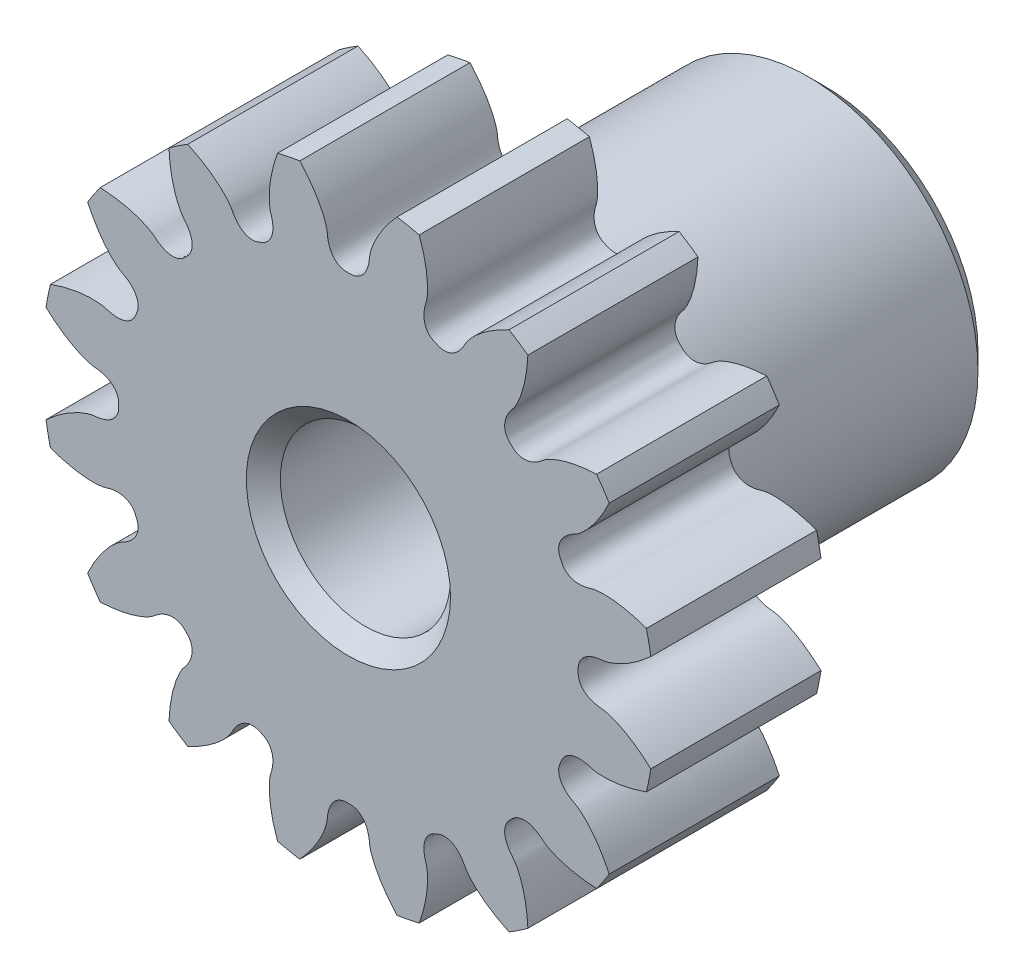
SolidWorks part; units mm, degrees
material "Plain Carbon Steel"
ref_plane "Front Plane" through (0, 0, 0) normal (0, 0, 1) x (1, 0, 0)
ref_plane "Top Plane" through (0, 0, 0) normal (0, 1, 0) x (1, 0, 0)
ref_plane "Right Plane" through (0, 0, 0) normal (1, 0, 0) x (0, 0, -1)
ref_axis "Axis1" through (0, 0, 55) along (0, 0, -1)
sketch "SketchRevolveSpur01" plane through (0, 0, 0) normal (1, 0, 0) x (0, 0, -1)
  line L0 (0, 0) -> (1, 0) construction
  line L1 (-2.5, 0) -> (-2.5, 9)
  line L2 (-2.5, 9) -> (2.5, 9)
  line L3 (2.5, 9) -> (2.5, 0)
  line L4 (2.5, 0) -> (-2.5, 0)
  dimension "Side1" = 2.5
  dimension "OutsideRadius" = 9
  dimension "Side2" = 2.5
revolve "Spur01" add sketch "SketchRevolveSpur01" angle 360 about L0
sketch "SketchToothSpur01" plane through (0, 0, 0) normal (0, 0, 1) x (1, 0, 0)
  arc A0 (8.93, 1.469) -> (8.93, -1.469) centre (0, 0) cw
  spline S0 degree 3 poles (8.93, -1.469) (8.852, -1.3959) (8.7347, -1.2926) (8.5758, -1.1667) (8.4638, -1.0839) (8.356, -1.0096) (8.2529, -0.9435) (8.1549, -0.8853) (8.0624, -0.8344) (7.9758, -0.7905) (7.8955, -0.7531) (7.8216, -0.7216) (7.7547, -0.6957) (7.6949, -0.6749) (7.6425, -0.6585) (7.5977, -0.6462) (7.5608, -0.6373) (7.5318, -0.6313) (7.4566, -0.6186) (7.3723, -0.6159) (7.2802, -0.5971) (7.2303, -0.5851) (7.1817, -0.5707) (7.1344, -0.554) (7.0881, -0.5345) (7.0427, -0.512) (6.998, -0.4858) (6.9542, -0.4551) (6.9112, -0.4189) (6.8697, -0.3762) (6.8308, -0.3256) (6.7965, -0.2661) (6.7692, -0.1978) (6.7539, -0.1268) (6.7487, -0.06) (6.7506, 0) (6.7487, 0.06) (6.7539, 0.1268) (6.7692, 0.1978) (6.7965, 0.2661) (6.8308, 0.3256) (6.8697, 0.3762) (6.9112, 0.4189) (6.9542, 0.4551) (6.998, 0.4858) (7.0427, 0.512) (7.0881, 0.5345) (7.1344, 0.554) (7.1817, 0.5707) (7.2303, 0.5851) (7.2802, 0.5971) (7.3723, 0.6159) (7.4566, 0.6186) (7.5318, 0.6313) (7.5608, 0.6373) (7.5977, 0.6462) (7.6425, 0.6585) (7.6949, 0.6749) (7.7547, 0.6957) (7.8216, 0.7216) (7.8955, 0.7531) (7.9758, 0.7905) (8.0624, 0.8344) (8.1549, 0.8853) (8.2529, 0.9435) (8.356, 1.0096) (8.4638, 1.0839) (8.5758, 1.1667) (8.7347, 1.2926) (8.852, 1.3959) (8.93, 1.469) knots 0 0 0 0 0.057702 0.084276 0.109331 0.132867 0.154885 0.175385 0.194366 0.211828 0.227772 0.242198 0.255105 0.266493 0.276364 0.284715 0.291548 0.296863 0.300659 0.332714 0.342111 0.351328 0.360412 0.369418 0.378417 0.387494 0.396754 0.406323 0.416348 0.426989 0.438404 0.450708 0.463926 0.47793 0.489703 0.5 0.510297 0.52207 0.536074 0.549292 0.561596 0.573011 0.583652 0.593677 0.603246 0.612506 0.621583 0.630582 0.639588 0.648672 0.657889 0.667286 0.699341 0.703137 0.708452 0.715285 0.723636 0.733507 0.744895 0.757802 0.772228 0.788172 0.805634 0.824615 0.845115 0.867133 0.890669 0.915724 0.942298 1 1 1 1
extrude "ToothExtrudeCutSpur01" cut sketch "SketchToothSpur01" against normal blind 2.5 and the other way blind 2.5
ref_axis "Axis2" through (9.9525, 0, 0) along (-1, 0, 0)
ref_plane "Plane1" through (0, 0, 0) normal (0, 0, -1) x (1, 0, 0)
pattern_circular "PatternSpur01" count 16 every 22.5 about axis through (0, 0, 55) along (0, 0, -1) of "ToothExtrudeCutSpur01"
sketch "HubSketchSide1" plane through (0, 0, 0) normal (1, 0, 0) x (0, 0, -1)
  line L0 (0, 0) -> (1, 0) construction
  line L1 (3, 5) -> (11, 5)
  line L2 (11, 5) -> (11.5, 4.5)
  line L3 (11.5, 4.5) -> (11.5, 0)
  line L4 (11.5, 0) -> (2.5, 0)
  line L5 (2.5, 0) -> (2.5, 5.5)
  arc A0 (2.5, 5.5) -> (3, 5) centre (3, 5.5) ccw
  dimension "HubFillet1" = 1
  dimension "HubRadius1" = 5
  dimension "HubChamferX1" = 0.5
  dimension "HubChamferY1" = 0.5
  dimension "HubFace1" = 11.5
  dimension "HubComponentFace1" = 2.5
revolve "HubRevolve1" add sketch "HubSketchSide1" angle 360 about L0
sketch "BoreRevolveSketch" plane through (0, 0, 0) normal (1, 0, 0) x (0, 0, -1)
  line L0 (0, 0) -> (1, 0) construction
  line L1 (-2.5, 0) -> (11.5, 0)
  line L2 (11.5, 0) -> (11.5, 3)
  line L3 (11.5, 3) -> (11, 2.5)
  line L4 (11, 2.5) -> (-2, 2.5)
  line L5 (-2, 2.5) -> (-2.5, 3)
  line L6 (-2.5, 3) -> (-2.5, 0)
  dimension "BoreSide1" = 11.5
  dimension "TaperSide1" = 3
  dimension "Chamfer1X" = 0.5
  dimension "Chamfer1Y" = 0.5
  dimension "BoreSide2" = 2.5
  dimension "TaperSide2" = 3
revolve "BoreRevolveCut" cut sketch "BoreRevolveSketch" angle 360 about L0
sketch "AuxiliarySketchSpur01" plane through (0, 0, 0) normal (0, 0, 1) x (1, 0, 0)
  circle A0 centre (0, 0) radius 8 construction
  circle A1 centre (0, 0) radius 7.5175 construction
  circle A2 centre (0, 0) radius 7.5201 construction
  circle A3 centre (0, 0) radius 9 construction
  circle A4 centre (0, 0) radius 6.75 construction
  dimension "PitchDiameter" = 16
  dimension "BaseDiameter" = 15.0351
  dimension "FormDiameter" = 15.0403
  dimension "MajorDiameter" = 18
  dimension "MinorDiameter" = 13.5
ref_point "Point1"
ref_point "Point2"
